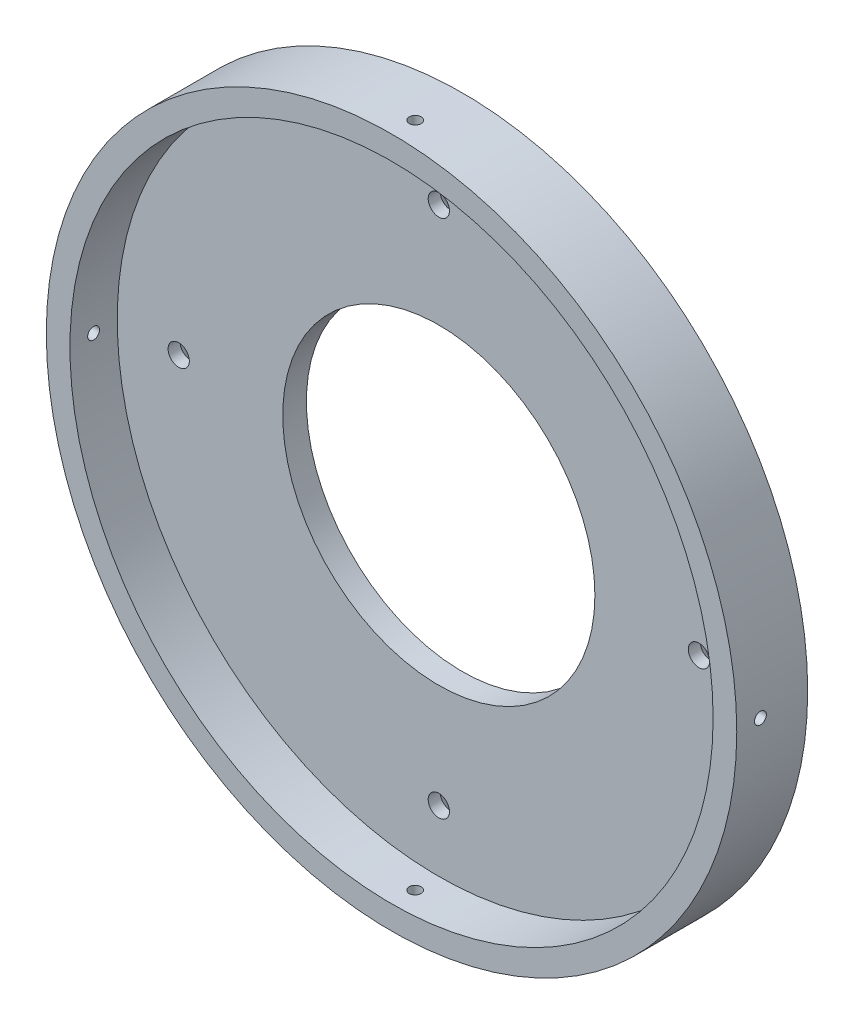
SolidWorks part; units mm, degrees
ref_plane "Front Plane" through (0, 0, 0) normal (0, 0, 1) x (1, 0, 0)
ref_plane "Top Plane" through (0, 0, 0) normal (0, 1, 0) x (1, 0, 0)
ref_plane "Right Plane" through (0, 0, 0) normal (1, 0, 0) x (0, 0, -1)
sketch "Sketch1" plane through (0, 0, 0) normal (0, 0, 1) x (1, 0, 0)
  circle A0 centre (0, 0) radius 73
  circle A1 centre (0, 0) radius 33
  dimension "D1" = 146
  dimension "D2" = 40
extrude "Boss-Extrude1" add sketch "Sketch1" along normal blind 5
sketch "Sketch2" plane through (0, 0, 5) normal (0, 0, 1) x (1, 0, 0)
  circle A0 centre (0, 0) radius 68
  circle A1 centre (0, 0) radius 73
  circle A2 centre (0, 0) radius 73
  dimension "D1" = 0
  dimension "D2" = 5
extrude "Boss-Extrude2" add sketch "Sketch2" along normal blind 10
sketch "Sketch3" plane through (0, 0, 0) normal (0, 1, 0) x (1, 0, 0)
  line L0 (-73, -15) -> (73, -15) construction
  circle A0 centre (0, -10) radius 1.25
  dimension "D2" = 2.5
  dimension "D1" = 5
extrude "Cut-Extrude1" cut sketch "Sketch3" against normal up to surface (73 mm away) up to face at (73, 0, 0)
pattern_circular "CirPattern1" count 4 over 360 about axis through (0, 0, 5) along (0, 0, -1) of "Cut-Extrude1"
sketch "Sketch9" plane through (0, 0, 0) normal (0, 0, -1) x (-1, 0, 0)
  point P0 (0, 55)
  point P4 (55, 0)
  point P6 (0, -55)
  point P8 (-55, 0)
  dimension "D1" = 55
  dimension "D2" = 0
  dimension "D3" = 55
  dimension "D4" = 55
  dimension "D5" = 55
hole_wizard "CSK for M4 Countersunk Flat Head Screw3" positions "Sketch9" profile "Sketch10" countersink size "M4" standard "ISO" end condition through all
sketch "Sketch10" plane through (0, 55, 0) normal (1, 0, 0) x (0, 1, 0)
  line L0 (0, 0) -> (0, 15)
  line L1 (0, 15) -> (2.25, 15)
  line L2 (2.25, 15) -> (2.25, 2.45)
  line L3 (2.25, 2.45) -> (4.7, 0)
  line L5 (4.7, 0) -> (0, 0)
  line L6 (-2.25, 2.45) -> (-4.7, 0) construction
  line L11 (0, -6.35) -> (0, 107.95) construction
  dimension "Thru Hole Dia." = 4.5
  dimension "Thru Hole Depth" = 15
  dimension "Near C'Sink Dia." = 9.4
  dimension "Near C'Sink Angle" = 90
